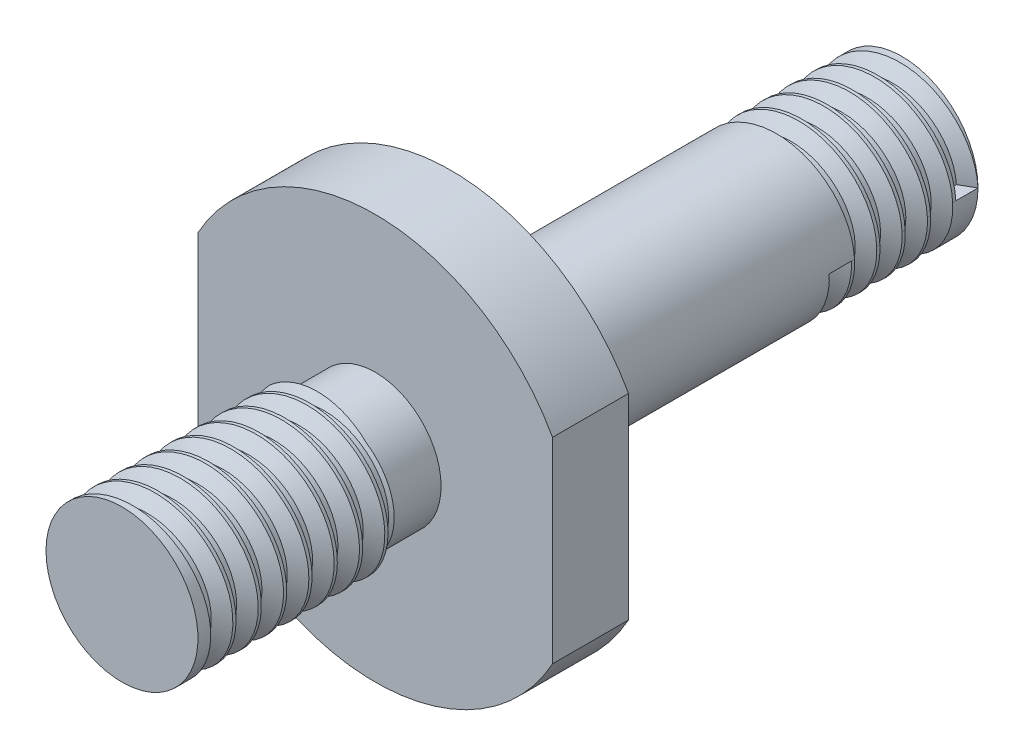
SolidWorks part; units mm, degrees
ref_plane "Front Plane" through (0, 0, 0) normal (0, 0, 1) x (1, 0, 0)
ref_plane "Top Plane" through (0, 0, 0) normal (0, 1, 0) x (1, 0, 0)
ref_plane "Right Plane" through (0, 0, 0) normal (1, 0, 0) x (0, 0, -1)
sketch "Sketch1" plane through (0, 0, 0) normal (0, 0, 1) x (1, 0, 0)
  circle A0 centre (0, 0) radius 1.5
extrude "Boss-Extrude1" add sketch "Sketch1" along normal blind 8.4
sketch "Sketch2" plane through (0, 0, 8.4) normal (0, 0, 1) x (1, 0, 0)
  circle A0 centre (0, 0) radius 2.5
extrude "Boss-Extrude2" add sketch "Sketch2" along normal blind 0.5
sketch "Sketch3" plane through (0, 0, 8.9) normal (0, 0, 1) x (1, 0, 0)
  line L0 (-3.5, 1.9365) -> (-3.5, -1.9365)
  line L1 (3.5, 1.9365) -> (3.5, -1.9365)
  arc A0 (-3.5, -1.9365) -> (3.5, -1.9365) centre (0, 0) ccw
  arc A1 (3.5, 1.9365) -> (-3.5, 1.9365) centre (0, 0) ccw
  point P6 (0, 0)
  point P7 (0, 0)
  point P8 (0, 0)
  point P9 (0, 0)
  point P10 (0, 0)
  point P11 (0, 0)
extrude "Boss-Extrude3" add sketch "Sketch3" along normal blind 1.5
sketch "Sketch4" plane through (0, 0, 10.4) normal (0, 0, 1) x (1, 0, 0)
  circle A0 centre (0, 0) radius 1.3
extrude "Boss-Extrude4" add sketch "Sketch4" along normal blind 1
sketch "Sketch5" plane through (0, 0, 11.4) normal (0, 0, 1) x (1, 0, 0)
  circle A0 centre (0, 0) radius 1.5
extrude "Boss-Extrude5" add sketch "Sketch5" along normal blind 4
thread "Thread1" pitch 0.5 method cut profile "Thread Profile1" start angle 0, offset 0, length 2.5, pitch 0.5, diameter 3
ref_plane "Plane1" through (1.5, 0, 0) normal (0, -1, 0) x (1, 0, 0)
sketch "Thread Profile1" plane through (1.5, 0, 0) normal (0, -1, 0) x (1, 0, 0)
  line L0 (0, 0) -> (0, 0.5) construction
  line L11 (0, 0) -> (0, 0.4375)
  line L12 (0, 0.4375) -> (-0.2706, 0.2812)
  line L13 (-0.2706, 0.2812) -> (-0.2706, 0.1562)
  line L15 (-0.2706, 0.1562) -> (0, 0)
  line L17 (-0.2706, 0.2187) -> (0, 0.2187) construction
  point P2 (0, 0)
  dimension "Pitch" = 0.5
  dimension "Profile_Angle" = 60
  dimension "Profile_Land" = 0.125
  dimension "Profile_Height" = 0.2706
thread "Thread2" pitch 0.5 method cut profile "Thread Profile2" start angle 0, offset 0, length 4, pitch 0.5, diameter 3
ref_plane "Plane2" through (-1.5, 0, 15.4) normal (0, -1, 0) x (-1, 0, 0)
sketch "Thread Profile2" plane through (-1.5, 0, 15.4) normal (0, -1, 0) x (-1, 0, 0)
  line L0 (0, 0) -> (0, 0.5) construction
  line L11 (0, 0) -> (0, 0.4375)
  line L12 (0, 0.4375) -> (-0.2706, 0.2812)
  line L13 (-0.2706, 0.2812) -> (-0.2706, 0.1562)
  line L15 (-0.2706, 0.1562) -> (0, 0)
  line L17 (-0.2706, 0.2187) -> (0, 0.2187) construction
  point P2 (0, 0)
  dimension "Pitch" = 0.5
  dimension "Profile_Angle" = 60
  dimension "Profile_Land" = 0.125
  dimension "Profile_Height" = 0.2706
